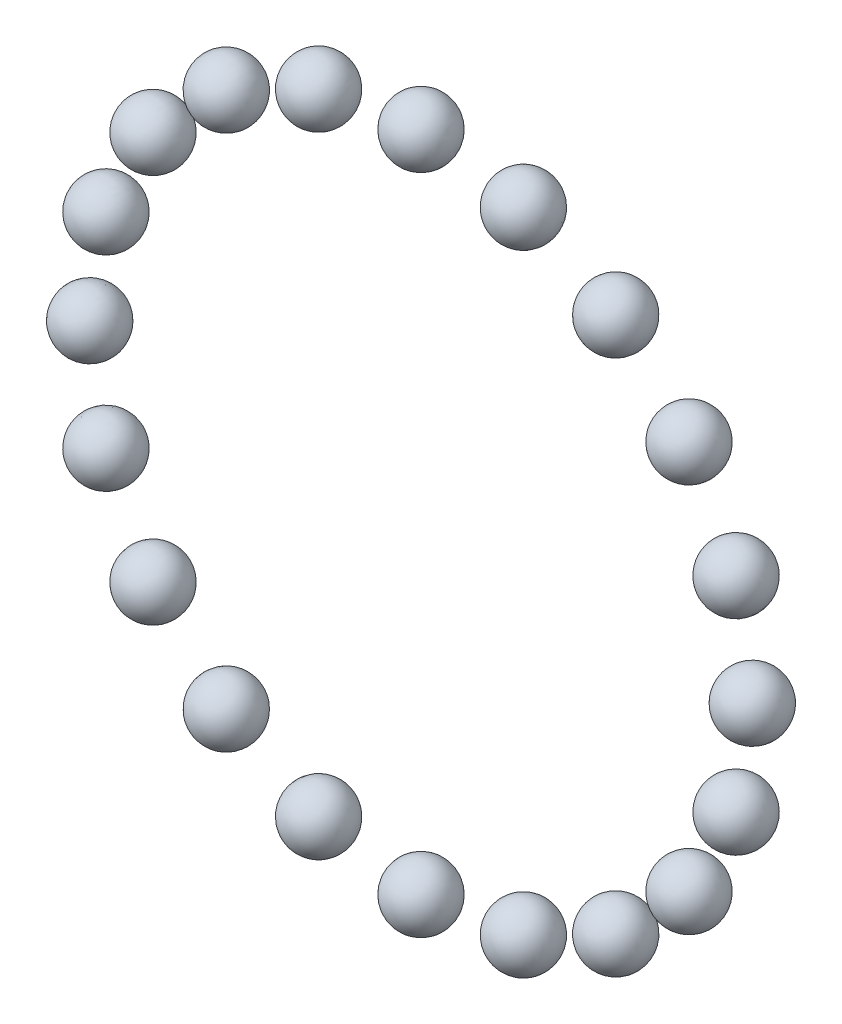
SolidWorks part; units mm, degrees
ref_plane "Front Plane" through (0, 0, 0) normal (0, 0, 1) x (1, 0, 0)
ref_plane "Top Plane" through (0, 0, 0) normal (0, 1, 0) x (1, 0, 0)
ref_plane "Right Plane" through (0, 0, 0) normal (1, 0, 0) x (0, 0, -1)
sketch "Sketch1" plane through (0, 0, 0) normal (0, 0, 1) x (1, 0, 0)
  circle A0 centre (0, 0) radius 32.5
  dimension "D1" = 65
sketch "Sketch2" plane through (0, 0, 0) normal (0, 0, 1) x (1, 0, 0)
  line L0 (-35.5, 0) -> (-29.5, 0)
  circle A0 centre (-32.5, 0) radius 3
  circle A1 centre (0, 0) radius 32.5 construction
  dimension "D1" = 6
ref_axis "Axis1" through (0, 0, 0) along (0, 0, 1)
revolve "Revolve1" add sketch "Sketch2" angle 360 about L0 region at (-32.5, 1.2732, 0)
pattern_circular "CirPattern1" count 20 over 360 about axis through (0, 0, 0) along (0, 0, 1) of bodies 101
